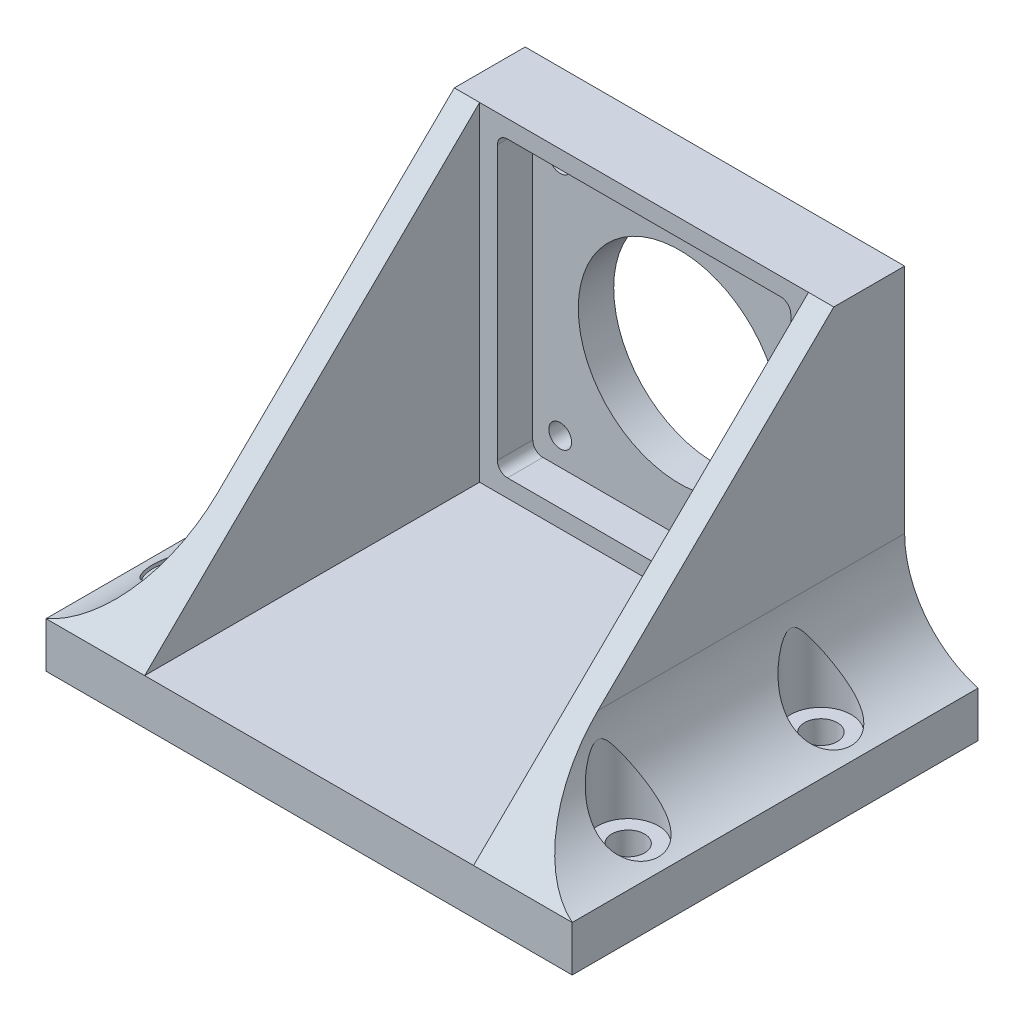
SolidWorks part; units mm, degrees
ref_plane "Front Plane" through (0, 0, 0) normal (0, 0, 1) x (1, 0, 0)
ref_plane "Top Plane" through (0, 0, 0) normal (0, 1, 0) x (1, 0, 0)
ref_plane "Right Plane" through (0, 0, 0) normal (1, 0, 0) x (0, 0, -1)
sketch "Sketch1" plane through (0, 0, 0) normal (0, 0, 1) x (1, 0, 0)
  line L1 (-32.5, 32.5) -> (32.5, 32.5)
  line L2 (-32.5, 32.5) -> (-32.5, -32.5)
  line L3 (-32.5, -32.5) -> (32.5, -32.5)
  line L4 (32.5, 32.5) -> (32.5, -32.5)
  line L5 (-32.5, 32.5) -> (32.5, -32.5) construction
  line L6 (-32.5, -32.5) -> (32.5, 32.5) construction
  circle A0 centre (0, 0) radius 20
  circle A1 centre (23.57, 23.57) radius 2.25
  circle A2 centre (-23.57, 23.57) radius 2.25
  circle A3 centre (-23.57, -23.57) radius 2.25
  circle A4 centre (23.57, -23.57) radius 2.25
  point P0 (0, 0)
  dimension "D1" = 2
  dimension "D2" = 2
extrude "Boss-Extrude1" add sketch "Sketch1" along normal blind 10
sketch "Sketch2" plane through (0, 0, 10) normal (0, 0, 1) x (1, 0, 0)
  line L0 (0, -32.5) -> (-52, -32.5)
  line L1 (-32.5, -32.5) -> (32.5, -32.5) construction
  line L2 (-52, -32.5) -> (-52, -42.5)
  line L3 (-52, -42.5) -> (52, -42.5)
  line L4 (52, -42.5) -> (52, -32.5)
  line L5 (52, -32.5) -> (0, -32.5)
extrude "Boss-Extrude2" add sketch "Sketch2" along normal blind 66.2 and the other way blind 10
sketch "Sketch4" plane through (32.5, 0, 0) normal (1, 0, 0) x (0, 0, -1)
  line L0 (0, -32.5) -> (-76.2, -32.5) construction
  line L1 (0, -32.5) -> (-76.2, -32.5)
  line L2 (0, -32.5) -> (0, 32.5) construction
  line L3 (-10, 32.5) -> (0, 32.5) construction
  line L4 (0, -32.5) -> (0, 32.5)
  line L5 (-10, 32.5) -> (0, 32.5)
  line L6 (-10, 32.5) -> (-76.2, -32.5)
extrude "Boss-Extrude3" add sketch "Sketch4" along normal blind 5
sketch "Sketch5" plane through (-32.5, 0, 0) normal (-1, 0, 0) x (0, 0, 1)
  line L0 (10, 32.5) -> (0, 32.5) construction
  line L1 (0, 32.5) -> (0, -32.5) construction
  line L2 (0, -32.5) -> (76.2, -32.5) construction
  line L3 (10, 32.5) -> (0, 32.5)
  line L4 (0, 32.5) -> (0, -32.5)
  line L5 (0, -32.5) -> (76.2, -32.5)
  line L6 (10, 32.5) -> (76.2, -32.5)
extrude "Boss-Extrude4" add sketch "Sketch5" along normal blind 5
fillet "Fillet1" radius 20 2 edges at (37.5, -32.5, 38.1) (-37.5, -32.5, 38.1)
sketch "Sketch3" plane through (0, -42.5, 0) normal (0, -1, 0) x (1, 0, 0)
  circle A0 centre (44, 19.05) radius 3.25
  circle A1 centre (-44, 19.05) radius 3.25
  circle A2 centre (-44, 57.15) radius 3.25
  circle A3 centre (44, 57.15) radius 3.25
  dimension "D1" = 2
  dimension "D2" = 2
extrude "Cut-Extrude1" cut sketch "Sketch3" against normal through all
ref_plane "Plane1" through (0, -11.5, 0) normal (0, 1, 0) x (1, 0, 0)
sketch "Sketch6" plane through (0, -11.5, 0) normal (0, 1, 0) x (1, 0, 0)
  circle A0 centre (44, -19.05) radius 3.25 construction
  circle A1 centre (44, -57.15) radius 3.25 construction
  circle A2 centre (-44, -57.15) radius 3.25 construction
  circle A3 centre (-44, -19.05) radius 3.25 construction
  circle A4 centre (44, -19.05) radius 3.25
  circle A5 centre (44, -57.15) radius 3.25
  circle A6 centre (-44, -57.15) radius 3.25
  circle A7 centre (-44, -19.05) radius 3.25
  circle A8 centre (-44, -19.05) radius 6
  circle A9 centre (-44, -57.15) radius 6
  circle A10 centre (44, -57.15) radius 6
  circle A11 centre (44, -19.05) radius 6
extrude "Cut-Extrude2" cut sketch "Sketch6" against normal up to surface (21 mm away) up to face at (0, -32.5, 43.1)
chamfer "Chamfer1" distance 1 angle 45 8 edges at (0, -42.5, 0) (-52, -42.5, 38.1) (0, -42.5, 76.2) (52, -42.5, 38.1) (44, -42.5, 15.8) (-44, -42.5, 15.8) (-44, -42.5, 53.9) (44, -42.5, 53.9)
sketch "Sketch7" plane through (0, 0, 10) normal (0, 0, 1) x (1, 0, 0)
  line L1 (-27, -29) -> (27, -29)
  line L2 (-29, -27) -> (-29, 27)
  line L3 (-27, 29) -> (27, 29)
  line L4 (29, -27) -> (29, 27)
  line L5 (-29, -29) -> (29, 29) construction
  line L6 (-29, 29) -> (29, -29) construction
  arc A0 (-29, -27) -> (-27, -29) centre (-27, -27) ccw
  arc A1 (27, -29) -> (29, -27) centre (27, -27) ccw
  arc A2 (29, 27) -> (27, 29) centre (27, 27) ccw
  arc A3 (-27, 29) -> (-29, 27) centre (-27, 27) ccw
  point P0 (0, 0)
  dimension "D2" = 2
  dimension "D1" = 58
extrude "Cut-Extrude3" cut sketch "Sketch7" against normal offset from surface (7 mm away) 3 up to face at (0, -14.2996, 0)
sketch "Sketch8" plane through (0, 0, 0) normal (0, 0, -1) x (-1, 0, 0)
  line L6 (-52, -32.5) -> (-52, -41.5)
  line L7 (-52, -41.5) -> (52, -41.5)
  line L8 (52, -41.5) -> (52, -32.5)
  line L9 (37.5, -13.2711) -> (37.5, 32.5)
  line L10 (37.5, 32.5) -> (-37.5, 32.5)
  line L11 (-37.5, 32.5) -> (-37.5, -13.2711)
  line L12 (-52, -32.5) -> (-52, -41.5)
  line L13 (-52, -41.5) -> (52, -41.5)
  line L14 (52, -41.5) -> (52, -32.5)
  line L15 (37.5, -13.2711) -> (37.5, 32.5)
  line L16 (37.5, 32.5) -> (-37.5, 32.5)
  line L17 (-37.5, 32.5) -> (-37.5, -13.2711)
  circle A0 centre (0, 0) radius 20 construction
  circle A1 centre (-23.57, -23.57) radius 2.25 construction
  arc A2 (37.5, -13.2711) -> (52, -32.5) centre (57.5, -13.2711) ccw
  arc A3 (-52, -32.5) -> (-37.5, -13.2711) centre (-57.5, -13.2711) ccw
  arc A4 (37.5, -13.2711) -> (52, -32.5) centre (57.5, -13.2711) ccw
  arc A5 (-52, -32.5) -> (-37.5, -13.2711) centre (-57.5, -13.2711) ccw
  circle A6 centre (-23.57, 23.57) radius 2.25 construction
  circle A7 centre (23.57, -23.57) radius 2.25 construction
  circle A8 centre (23.57, 23.57) radius 2.25 construction
  circle A9 centre (0, 0) radius 20
  circle A10 centre (-23.57, -23.57) radius 2.25
  circle A11 centre (-23.57, 23.57) radius 2.25
  circle A12 centre (23.57, -23.57) radius 2.25
  circle A13 centre (23.57, 23.57) radius 2.25
  dimension "D1" = 0
extrude "Boss-Extrude5" add sketch "Sketch8" along normal blind 4
